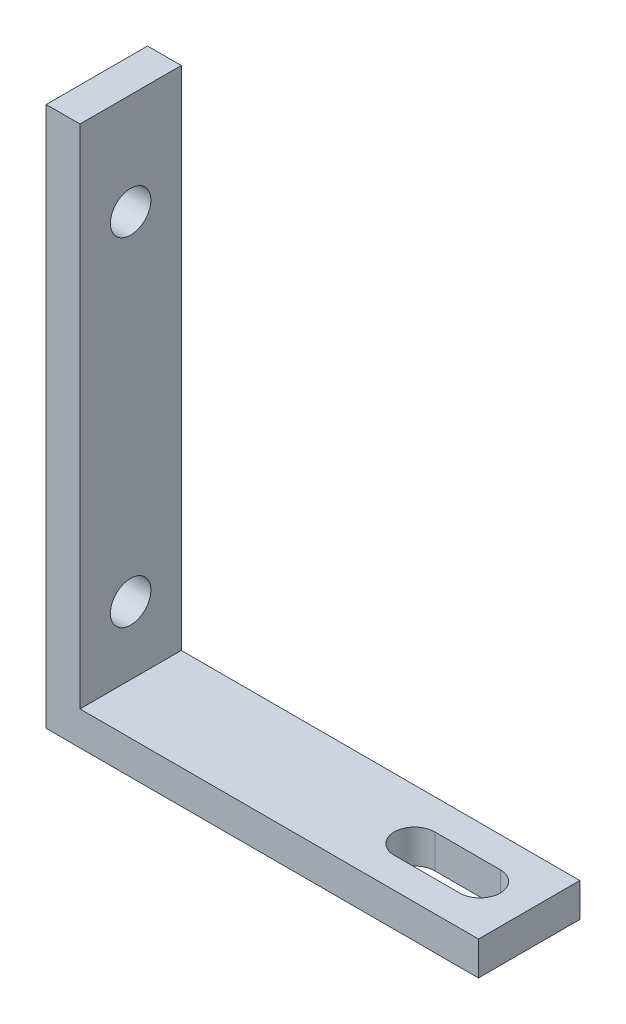
SolidWorks part; units mm, degrees
ref_plane "Front Plane" through (0, 0, 0) normal (0, 0, 1) x (1, 0, 0)
ref_plane "Top Plane" through (0, 0, 0) normal (0, 1, 0) x (1, 0, 0)
ref_plane "Right Plane" through (0, 0, 0) normal (1, 0, 0) x (0, 0, -1)
sketch "Sketch1" plane through (0, 0, 0) normal (0, 1, 0) x (1, 0, 0)
  line L1 (-30.1722, 4.0464) -> (33.8278, 4.0464)
  line L2 (-30.1722, 4.0464) -> (-30.1722, -10.9536)
  line L3 (-30.1722, -10.9536) -> (33.8278, -10.9536)
  line L4 (33.8278, 4.0464) -> (33.8278, -10.9536)
  dimension "D1" = 15
  dimension "D2" = 64
extrude "Boss-Extrude1" add sketch "Sketch1" along normal blind 5
sketch "Sketch3" plane through (0, 5, 0) normal (0, 1, 0) x (1, 0, 0)
  line L0 (-30.1722, 4.0464) -> (-25.1722, 4.0464)
  line L1 (33.8278, 4.0464) -> (-30.1722, 4.0464) construction
  line L2 (-30.1722, -10.9536) -> (-25.1722, -10.9536)
  line L3 (-30.1722, -10.9536) -> (33.8278, -10.9536) construction
  line L4 (-25.1722, 4.0464) -> (-25.1722, -10.9536)
  line L5 (-30.1722, 4.0464) -> (-30.1722, -10.9536)
extrude "Boss-Extrude2" add sketch "Sketch3" along normal blind 75
sketch "Sketch4" plane through (-30.1722, 0, 0) normal (-1, 0, 0) x (0, 0, 1)
  line L0 (3.4536, 80) -> (3.4536, 0)
  line L1 (-4.0464, 80) -> (10.9536, 80) construction
  line L2 (-4.0464, 0) -> (10.9536, 0) construction
  line L3 (3.4536, 0) -> (3.4536, 15)
  line L4 (3.4536, 80) -> (3.4536, 65)
hole_wizard "Ø6.0mm Dowel Hole1" positions "Sketch5" profile "Sketch6" hole size "Ø6.0" standard "ANSI Metric" end condition up to next
sketch "Sketch5" plane through (-30.1722, 0, 0) normal (-1, 0, 0) x (0, 0, 1)
  point P0 (3.4536, 65)
  point P3 (3.4536, 15)
sketch "Sketch6" plane through (-30.1722, 65, 3.4536) normal (0, 1, 0) x (0, 0, 1)
  line L0 (0, 0) -> (0, 5)
  line L1 (0, 5) -> (3, 5)
  line L2 (3, 5) -> (3, 0)
  line L5 (3, 0) -> (0, 0)
  line L11 (0, -6.35) -> (0, 107.95) construction
  dimension "Thru Hole Dia." = 6
  dimension "Thru Hole Depth" = 5
sketch "Sketch7" plane through (0, 0, 0) normal (0, -1, 0) x (1, 0, 0)
  line L0 (-30.1722, 3.4536) -> (33.8278, 3.4536)
  line L1 (-30.1722, -4.0464) -> (-30.1722, 10.9536) construction
  line L2 (33.8278, 10.9536) -> (33.8278, -4.0464) construction
hole_wizard "Ø6.0mm Dowel Slot1" positions "Sketch8" profile "Sketch9" size "Ø6.0" standard "ANSI Metric" slot yes end condition up to next
sketch "Sketch8" plane through (0, 5, 0) normal (0, 1, 0) x (1, 0, 0)
  line L0 (13.8542, -3.4536) -> (29.5542, -3.4537) construction
  point P0 (21.7042, -3.4537)
  point P5 (0, 0)
  dimension "D1" = 15.7
sketch "Sketch9" plane through (21.7042, 5, 3.4537) normal (1, 0, 0) x (0, 0, 1)
  line L0 (0, 0) -> (0, 5)
  line L1 (0, 5) -> (3, 5)
  line L2 (3, 5) -> (3, 0)
  line L5 (3, 0) -> (0, 0)
  line L11 (0, -6.35) -> (0, 107.95) construction
  dimension "Thru Hole Dia." = 6
  dimension "Thru Hole Depth" = 5
